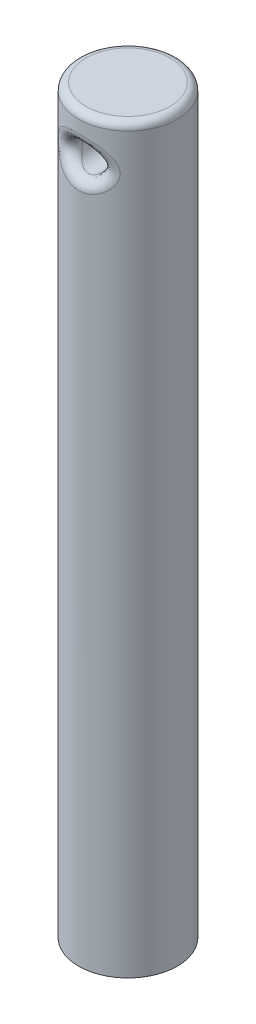
SolidWorks part; units mm, degrees
ref_plane "Front Plane" through (0, 0, 0) normal (0, 0, 1) x (1, 0, 0)
ref_plane "Top Plane" through (0, 0, 0) normal (0, 1, 0) x (1, 0, 0)
ref_plane "Right Plane" through (0, 0, 0) normal (1, 0, 0) x (0, 0, -1)
sketch "Sketch1" plane through (0, 0, 0) normal (0, 1, 0) x (1, 0, 0)
  circle A0 centre (0, 0) radius 10
  dimension "D1" = 20
extrude "Boss-Extrude1" add sketch "Sketch1" along normal blind 150
fillet "Fillet1" radius 1.5 1 edges at (0, 150, 10)
sketch "Sketch2" plane through (0, 0, 0) normal (0, 0, 1) x (1, 0, 0)
  line L0 (0, 150) -> (0, 141) construction
  line L1 (8.5, 150) -> (-8.5, 150) construction
  circle A0 centre (0, 141) radius 3
  dimension "D1" = 6
  dimension "D2" = 9
extrude "Cut-Extrude1" cut sketch "Sketch2" against normal through all both and the other way through all
fillet "Fillet3" radius 2 2 edges at (0.5429, 138.0495, -9.9853) (-2.9501, 141.5447, 9.5549)
